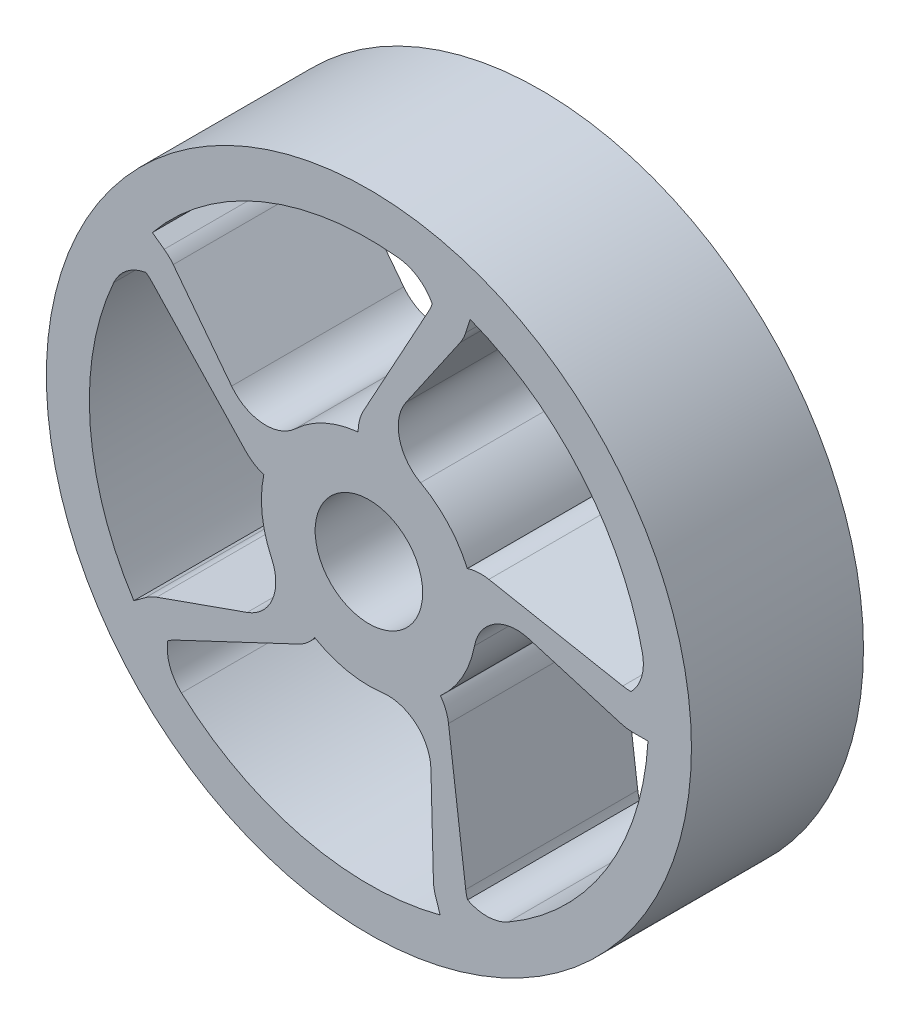
SolidWorks part; units mm, degrees
ref_plane "Front Plane" through (0, 0, 0) normal (0, 0, 1) x (1, 0, 0)
ref_plane "Top Plane" through (0, 0, 0) normal (0, 1, 0) x (1, 0, 0)
ref_plane "Right Plane" through (0, 0, 0) normal (1, 0, 0) x (0, 0, -1)
sketch "Sketch1" plane through (0, 0, 0) normal (0, 0, 1) x (1, 0, 0)
  line L0 (129.7102, 8.6759) -> (119.9567, 8.6251)
  line L1 (119.9567, 8.6251) -> (120.0401, -7.3747)
  line L2 (31.8314, 126.0427) -> (28.8657, 116.7509)
  line L3 (47.0738, 121.1778) -> (44.1082, 111.886)
  line L4 (28.8657, 116.7509) -> (44.1082, 111.886)
  line L5 (129.7935, -7.3239) -> (120.0401, -7.3747)
  line L6 (48.3339, -120.6807) -> (45.2716, -111.4203)
  line L7 (45.2716, -111.4203) -> (30.0807, -116.4438)
  line L8 (33.143, -125.7042) -> (30.0807, -116.4438)
  line L9 (-99.8382, -83.2607) -> (-91.9773, -77.4866)
  line L10 (-91.9773, -77.4866) -> (-101.4492, -64.5915)
  line L11 (-109.31, -70.3656) -> (-101.4492, -64.5915)
  line L12 (-110.0373, 69.2228) -> (-102.1167, 63.5309)
  line L13 (-102.1167, 63.5309) -> (-92.7797, 76.524)
  line L14 (-100.7003, 82.2159) -> (-92.7797, 76.524)
  circle A0 centre (0, 0) radius 150
  arc A1 (31.8314, 126.0427) -> (-100.7003, 82.2159) centre (0, 0) ccw
  arc A2 (-110.0373, 69.2228) -> (-109.31, -70.3656) centre (0, 0) ccw
  arc A3 (-99.8382, -83.2607) -> (33.143, -125.7042) centre (0, 0) ccw
  arc A4 (48.3339, -120.6807) -> (129.7935, -7.3239) centre (0, 0) ccw
  arc A5 (129.7102, 8.6759) -> (47.0738, 121.1778) centre (0, 0) ccw
  point P26 (0, 0)
  dimension "D1" = 300
  dimension "D2" = 20
  dimension "D3" = 5
extrude "Boss-Extrude1" add sketch "Sketch1" along normal blind 80
sketch "Sketch2" plane through (0, 0, 0) normal (0, 0, 1) x (1, 0, 0)
  line L0 (-5, 55) -> (5, 55)
  line L1 (5, 49.7494) -> (5, 55)
  line L2 (-5, 49.7494) -> (-5, 55)
  line L3 (50.763, 21.7512) -> (53.8532, 12.2407)
  line L4 (45.7694, 20.1287) -> (50.763, 21.7512)
  line L5 (48.8595, 10.6181) -> (53.8532, 12.2407)
  line L6 (36.3733, -41.557) -> (28.2831, -47.4349)
  line L7 (33.287, -37.3092) -> (36.3733, -41.557)
  line L8 (25.1969, -43.187) -> (28.2831, -47.4349)
  line L9 (-28.2831, -47.4349) -> (-36.3733, -41.557)
  line L10 (-25.1969, -43.187) -> (-28.2831, -47.4349)
  line L11 (-33.287, -37.3092) -> (-36.3733, -41.557)
  line L12 (-53.8532, 12.2407) -> (-50.763, 21.7512)
  line L13 (-48.8595, 10.6181) -> (-53.8532, 12.2407)
  line L14 (-45.7694, 20.1287) -> (-50.763, 21.7512)
  arc A0 (-5, 49.7494) -> (-45.7694, 20.1287) centre (0, 0) ccw
  arc A1 (-48.8595, 10.6181) -> (-33.287, -37.3092) centre (0, 0) ccw
  arc A2 (45.7694, 20.1287) -> (5, 49.7494) centre (0, 0) ccw
  arc A3 (-25.1969, -43.187) -> (25.1969, -43.187) centre (0, 0) ccw
  arc A4 (33.287, -37.3092) -> (48.8595, 10.6181) centre (0, 0) ccw
  point P25 (0, 0)
  dimension "D1" = 100
  dimension "D2" = 5
extrude "Boss-Extrude2" add sketch "Sketch2" along normal blind 80 separate body
loft "Loft1" add section face at (0, 55, 40) section face at (36.4869, 114.3184, 40) connector at (-5, 55, 80) connector at (28.8657, 116.7509, 80)
pattern_circular "CirPattern1" count 5 over 360 about axis through (0, 0, 80) along (0, 0, 1) of bodies 103
combine bodies "Combine1" bodies to combine 107 102 101 103 104 105 106
fillet "Fillet1" radius 20 20 edges
fillet "Fillet2" radius 20 5 edges at (-45.7694, 20.1287, 40) (5, 49.7494, 40) (48.8595, 10.6181, 40) (25.1969, -43.187, 40) (-33.287, -37.3092, 40)
fillet "Fillet3" radius 20 5 edges at (-99.8382, -83.2607, 40) (48.3339, -120.6807, 40) (129.7102, 8.6759, 40) (31.8314, 126.0427, 40) (-110.0373, 69.2228, 40)
sketch "Sketch3" plane through (0, 0, 80) normal (0, 0, 1) x (1, 0, 0)
  circle A0 centre (0, 0) radius 25
  dimension "D1" = 50
extrude "Cut-Extrude1" cut sketch "Sketch3" against normal blind 80
